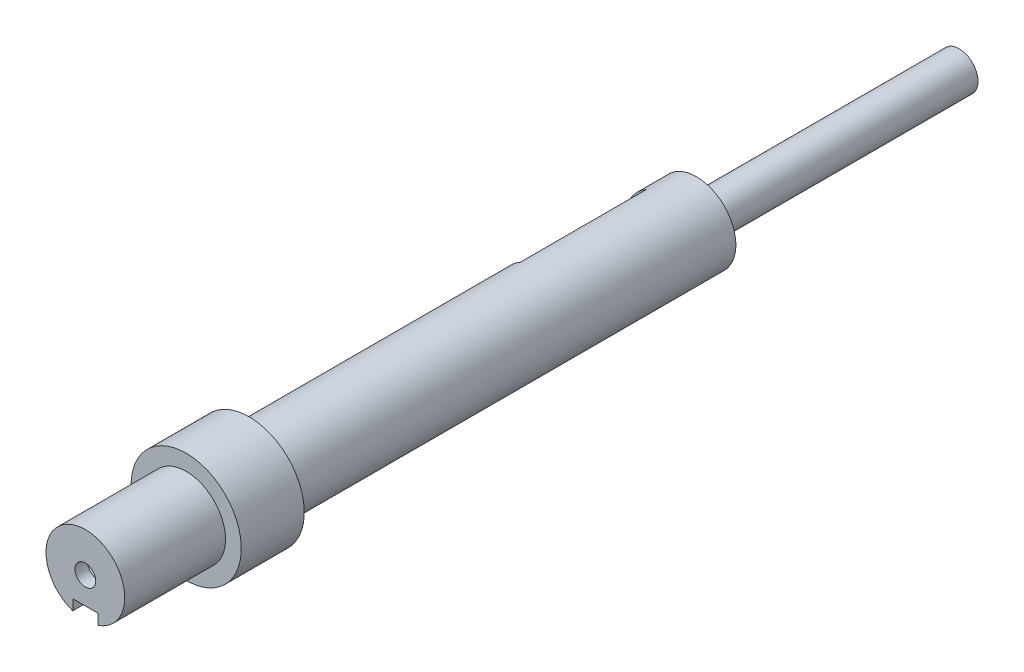
SolidWorks part; units mm, degrees
ref_plane "Plan de face" through (0, 0, 0) normal (0, 0, 1) x (1, 0, 0)
ref_plane "Plan de dessus" through (0, 0, 0) normal (0, 1, 0) x (1, 0, 0)
ref_plane "Plan de droite" through (0, 0, 0) normal (1, 0, 0) x (0, 0, -1)
sketch "Esquisse1" plane through (0, 0, 0) normal (0, 0, 1) x (1, 0, 0)
  circle A0 centre (0, 0) radius 30
  dimension "D1" = 60
extrude "Boss.-Extru.1" add sketch "Esquisse1" along normal blind 15
sketch "Esquisse2" plane through (0, 0, 0) normal (0, 0, -1) x (-1, 0, 0)
  circle A0 centre (0, 0) radius 12.5
  dimension "D1" = 25
extrude "Boss.-Extru.2" add sketch "Esquisse2" along normal blind 184
sketch "Esquisse4" plane through (0, 0, 15) normal (0, 0, 1) x (1, 0, 0)
  line L1 (115, 20) -> (-115, 20)
  line L2 (115, 20) -> (115, -20)
  line L3 (115, -20) -> (-115, -20)
  line L4 (-115, 20) -> (-115, -20)
  line L5 (115, 20) -> (-115, -20) construction
  line L6 (115, -20) -> (-115, 20) construction
  point P0 (0, 0)
  dimension "D1" = 40
  dimension "D2" = 230
extrude "Boss.-Extru.3" [suppressed] add sketch "Esquisse4" along normal blind 5
extrude "Enlèv. mat.-Extru.1" cut sketch "Esquisse4<2>" against normal blind 5
sketch "Esquisse4<2>" plane through (0, 0, 15) normal (0, 0, 1) x (1, 0, 0) same geometry as "Esquisse4"
sketch "Esquisse6" plane through (0, 0, 0) normal (0, 0, -1) x (-1, 0, 0)
  circle A2 centre (0, 0) radius 20.5
  circle A3 centre (0, 0) radius 20.5 construction
  dimension "D1" = 8
hole_wizard "Chambrage pour vis à tête hexagonale M51" positions "Esquisse15" profile "Esquisse14" counterbore size "M5" standard "Ansi Metric" end condition through all
sketch "Esquisse15" plane through (0, 0, 0) normal (0, 0, -1) x (-1, 0, 0)
  circle A0 centre (0, 0) radius 20.5 construction
  point P0 (20.5, 0)
  point P4 (-20.5, 0)
sketch "Esquisse14" plane through (-20.5, 0, 0) normal (1, 0, 0) x (0, 1, 0)
  line L0 (0, 0) -> (0, 15)
  line L1 (0, 15) -> (2.75, 15)
  line L2 (2.75, 3.605) -> (2.75, 15)
  line L3 (2.75, 3.605) -> (2.775, 3.58)
  line L4 (2.775, 3.58) -> (6.12, 3.58)
  line L5 (6.12, 3.58) -> (6.12, 0)
  line L7 (0, 0) -> (6.12, 0)
  line L9 (-2.75, 3.605) -> (-2.775, 3.58) construction
  line L11 (0, -6.35) -> (0, 107.95) construction
  dimension "Diamètre du perçage jusqu'au prochain" = 5.5
  dimension "Profondeur du perçage jusqu'au prochain" = 15
  dimension "Diamètre du chambrage" = 12.24
  dimension "Profondeur du chambrage" = 3.58
  dimension "Diamètre du fraisage milieu" = 5.55
  dimension "Angle du fraisage milieu" = 90
sketch "Esquisse17" plane through (0, 0, -184) normal (0, 0, -1) x (-1, 0, 0)
  circle A0 centre (0, 0) radius 6
  dimension "D1" = 12
extrude "Boss.-Extru.4" add sketch "Esquisse17" along normal blind 83.38
sketch "Esquisse18" plane through (0, 0, -267.38) normal (0, 0, -1) x (-1, 0, 0)
  line L0 (6.9654, 0) -> (-3.391, 0) construction
  line L1 (-3.391, 1.5) -> (6.9654, 1.5)
  line L2 (-3.391, 1.5) -> (-3.391, -1.5)
  line L3 (-3.391, -1.5) -> (6.9654, -1.5)
  line L4 (6.9654, 1.5) -> (6.9654, -1.5)
  line L5 (-3.391, 1.5) -> (6.9654, -1.5) construction
  line L6 (-3.391, -1.5) -> (6.9654, 1.5) construction
  point P0 (-0.771, 0)
  dimension "D1" = 3
  dimension "D2" = 2.62
extrude "Enlèv. mat.-Extru.2" cut sketch "Esquisse18" against normal blind 3
sketch "Esquisse19" plane through (0, 0, -184) normal (0, 0, -1) x (-1, 0, 0)
  line L0 (6, 10.9659) -> (6, -10.9659)
  line L1 (6, 10.9659) -> (13.9334, 10.9659)
  line L2 (6, -10.9659) -> (13.9334, -10.9659)
  line L3 (13.9334, 10.9659) -> (13.9334, -10.9659)
  circle A0 centre (0, 0) radius 12.5 construction
  circle A1 centre (0, 0) radius 12.5 construction
extrude "Enlèv. mat.-Extru.3" cut sketch "Esquisse19" against normal blind 50
sketch "Esquisse21" plane through (0, 0, -184) normal (0, 0, -1) x (-1, 0, 0)
  circle A0 centre (0, 0) radius 12.5
extrude "Boss.-Extru.6" add sketch "Esquisse21" against normal blind 10
sketch "Esquisse26" plane through (0, 0, -134) normal (0, 0, -1) x (-1, 0, 0)
  circle A0 centre (0, 0) radius 17.5
  dimension "D1" = 35
extrude "Boss.-Extru.8" add sketch "Esquisse26" against normal blind 112
sketch "Esquisse27" plane through (0, 0, -134) normal (0, 0, -1) x (-1, 0, 0)
  circle A0 centre (0, 0) radius 17.5
  circle A1 centre (0, 0) radius 12.5
  arc M2 (6, -10.9659) -> (6, 10.9659) centre (0, 0) cw
  circle M3 centre (0, 0) radius 17.5
  dimension "D1" = 25
extrude "Enlèv. mat.-Extru.5" cut sketch "Esquisse27" against normal blind 92 contours A1 M3 M2 region at (17.005, 0, -134)
sketch "Esquisse28" plane through (0, 0, 15) normal (0, 0, 1) x (1, 0, 0)
  circle A0 centre (0, 0) radius 30
  dimension "D1" = 60
extrude "Enlèv. mat.-Extru.6" cut sketch "Esquisse28" against normal blind 15
sketch "Esquisse29" plane through (0, 0, 0) normal (0, 0, 1) x (1, 0, 0)
  line L0 (0, 0) -> (0, -17.5) construction
  line L1 (-4, -8.5) -> (4, -8.5)
  line L2 (-4, -8.5) -> (-4, -15.8)
  line L3 (-4, -15.8) -> (4, -15.8)
  line L4 (4, -8.5) -> (4, -15.8)
  line L5 (-4, -8.5) -> (4, -15.8) construction
  line L6 (-4, -15.8) -> (4, -8.5) construction
  circle A0 centre (0, 0) radius 12.5
  circle A1 centre (0, 0) radius 17.5 construction
  circle M6 centre (0, 0) radius 12.5
  dimension "D1" = 25
  dimension "D2" = 15.8
  dimension "D3" = 8
  dimension "D4" = 4
  dimension "D5" = 8.5
extrude "Boss.-Extru.9" add sketch "Esquisse29" along normal blind 10 contours A0 L2 L1 L4 M6 region at (0, 0.6832, 0)
hole_wizard "Dégagement M61" positions "Esquisse31" profile "Esquisse30" hole size "M6" standard "JIS"
sketch "Esquisse31" plane through (0, 0, 10) normal (0, 0, 1) x (1, 0, 0)
  point P0 (0, 0)
sketch "Esquisse30" plane through (0, 0, 10) normal (1, 0, 0) x (0, -1, 0)
  line L0 (0, 0) -> (0, 5.9053)
  line L1 (0, 5.9053) -> (3.3, 4)
  line L2 (3.3, 4) -> (3.3, 0)
  line L5 (3.3, 0) -> (0, 0)
  line L10 (0, 5.9053) -> (-3.3, 4) construction
  line L11 (0, -6.35) -> (0, 107.95) construction
  dimension "Diamètre du perçage" = 6.6
  dimension "Profondeur du perçage" = 4
  dimension "Angle de pointe" = 120
